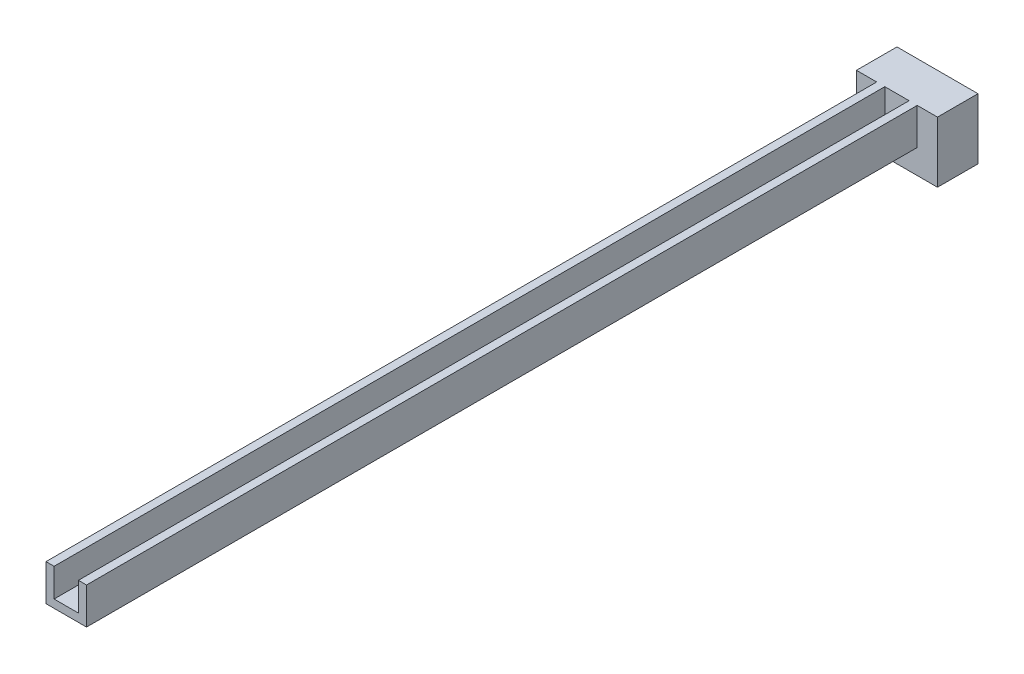
SolidWorks part; units mm, degrees
ref_plane "正面" through (0, 0, 0) normal (0, 0, 1) x (1, 0, 0)
ref_plane "平面" through (0, 0, 0) normal (0, 1, 0) x (1, 0, 0)
ref_plane "右側面" through (0, 0, 0) normal (1, 0, 0) x (0, 0, -1)
sketch "ｽｹｯﾁ1" plane through (0, 0, 0) normal (0, 0, 1) x (1, 0, 0)
  line L0 (-5, 9) -> (-5, 0)
  line L1 (-5, 0) -> (5, 0)
  line L2 (5, 0) -> (5, 9)
  line L3 (5, 9) -> (3, 9)
  line L4 (3, 9) -> (3, 2)
  line L5 (3, 2) -> (-3, 2)
  line L6 (-3, 2) -> (-3, 9)
  line L7 (-3, 9) -> (-5, 9)
  dimension "D1" = 9
  dimension "D2" = 9
  dimension "D3" = 10
  dimension "D4" = 5
  dimension "D5" = 2
  dimension "D6" = 2
  dimension "D7" = 2
extrude "ﾎﾞｽ - 押し出し1" add sketch "ｽｹｯﾁ1" along normal blind 245
sketch "ｽｹｯﾁ2" plane through (0, 0, 0) normal (0, -1, 0) x (1, 0, 0)
  line L0 (-5, 245) -> (5, 245) construction
  circle A0 centre (0, 225) radius 2.5
  circle A1 centre (0, 217) radius 2.5
  circle A2 centre (0, 122.5) radius 2.5
  circle A3 centre (0, 209) radius 2.5
  circle A4 centre (0, 193) radius 2.5
  circle A5 centre (0, 161) radius 2.5
  dimension "D1" = 20
  dimension "D3" = 5
  dimension "D4" = 5
  dimension "D5" = 5
  dimension "D6" = 122.5
  dimension "D7" = 5
  dimension "D8" = 8
  dimension "D9" = 5
  dimension "D10" = 16
  dimension "D11" = 5
  dimension "D12" = 32
  dimension "D2" = 28
extrude "ｶｯﾄ - 押し出し1" cut sketch "ｽｹｯﾁ2" against normal through all
ref_plane "平面1" through (0, 0, 122.5) normal (0, 0, 1) x (1, 0, 0)
mirror "ﾐﾗｰ1" about plane through (0, 0, 122.5) normal (0, 0, 1) of "ｶｯﾄ - 押し出し1"
sketch "ｽｹｯﾁ3" plane through (0, 0, 0) normal (0, -1, 0) x (1, 0, 0)
  line L0 (-5, 0) -> (-5, 40)
  line L1 (-5, 245) -> (-5, 0) construction
  line L2 (-5, 40) -> (5, 40)
  line L3 (5, 245) -> (5, 0) construction
  line L4 (5, 40) -> (5, 0)
  line L5 (5, 0) -> (-5, 0)
  dimension "D1" = 40
extrude "ｶｯﾄ - 押し出し2" cut sketch "ｽｹｯﾁ3" against normal through all both
sketch "ｽｹｯﾁ5" plane through (0, 0, 40) normal (0, 0, -1) x (-1, 0, 0)
  line L0 (-10, 9) -> (-10, -6)
  line L1 (-10, -6) -> (10, -6)
  line L2 (10, -6) -> (10, 9)
  line L3 (10, 9) -> (-10, 9)
  dimension "D1" = 20
  dimension "D2" = 10
  dimension "D3" = 15
  dimension "D4" = 9
extrude "ﾎﾞｽ - 押し出し3" add sketch "ｽｹｯﾁ5" along normal blind 10
equation "\"D2@ｽｹｯﾁ5\"=\"D1@ｽｹｯﾁ5\"/2"
